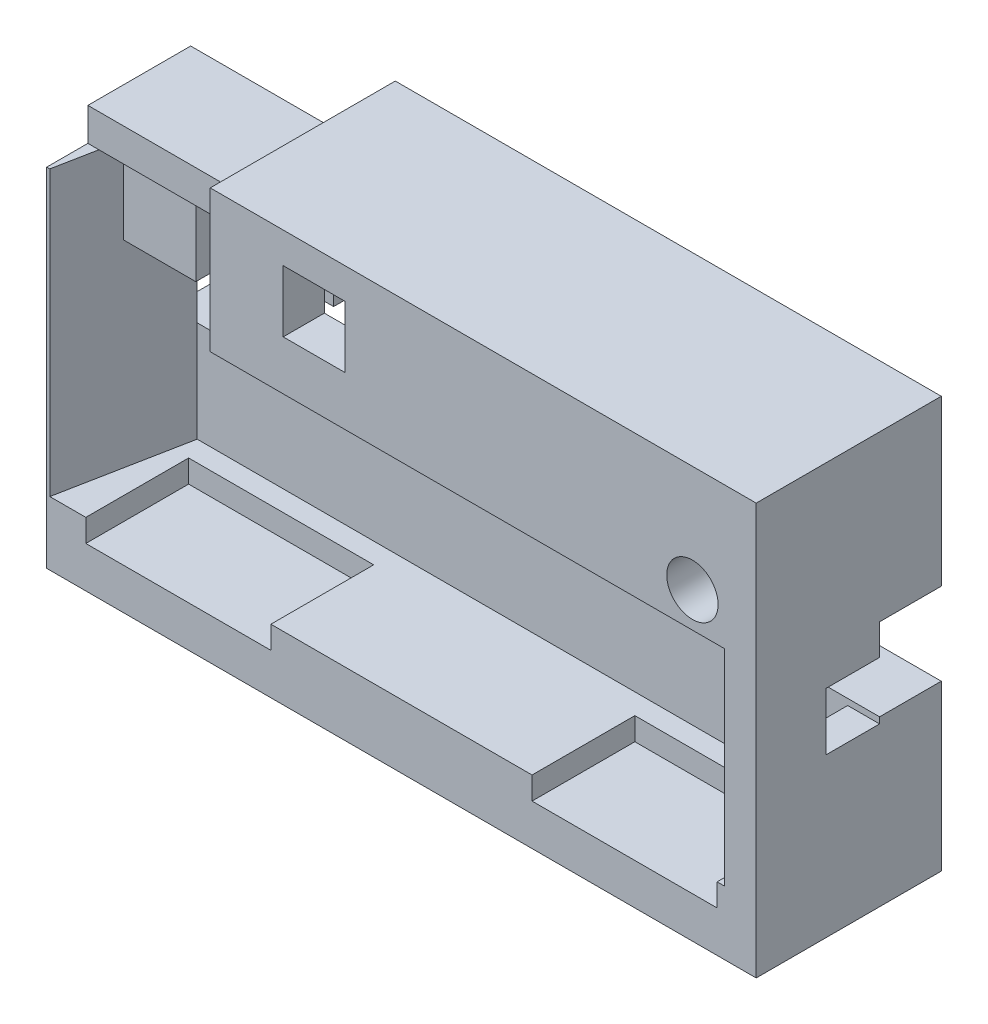
SolidWorks part; units mm, degrees
ref_plane "Ebene vorne" through (0, 0, 0) normal (0, 0, 1) x (1, 0, 0)
ref_plane "Ebene oben" through (0, 0, 0) normal (0, 1, 0) x (1, 0, 0)
ref_plane "Ebene rechts" through (0, 0, 0) normal (1, 0, 0) x (0, 0, -1)
sketch "Sketch1" plane through (0, 0, 0) normal (0, 0, 1) x (1, 0, 0)
  line L1 (-17.25, 10) -> (17.25, 10)
  line L2 (-17.25, 10) -> (-17.25, -10)
  line L3 (-17.25, -10) -> (17.25, -10)
  line L4 (17.25, 10) -> (17.25, -10)
  line L5 (-17.25, 10) -> (17.25, -10) construction
  line L6 (-17.25, -10) -> (17.25, 10) construction
  point P0 (0, 0)
  dimension "D1" = 34.5
  dimension "D2" = 20
extrude "Boss-Extrude1" add sketch "Sketch1" along normal blind 9
sketch "Sketch3" plane through (0, 0, 9) normal (0, 0, 1) x (1, 0, 0)
  line L1 (15.7, -6.9) -> (15.7, 3.1)
  line L3 (-15.7, 6.9) -> (-15.7, -6.9)
  line L6 (-15.7, 6.9) -> (-9.3, 6.9)
  line L7 (-15.7, -6.9) -> (15.7, -6.9)
  line L9 (-17.25, 10) -> (-17.25, -10) construction
  line L10 (-9.3, 6.9) -> (-9.3, 3.1)
  line L11 (-9.3, 3.1) -> (15.7, 3.1)
  point P2 (0, -6.9)
  dimension "D1" = 6.9
  dimension "D2" = 10
  dimension "D3" = 31.4
  dimension "D4" = 1.55
  dimension "D5" = 13.8
  dimension "D6" = 25
extrude "Cut-Extrude1" cut sketch "Sketch3" against normal blind 6
sketch "Sketch5" plane through (17.25, 0, 0) normal (1, 0, 0) x (0, 0, -1)
  line L0 (0, -2) -> (0, 2)
  line L1 (-3, 2) -> (0, 2)
  line L2 (-3, 2) -> (-3, -2)
  line L3 (-3, -2) -> (0, -2)
  point P0 (0, 0)
  dimension "D1" = 3
  dimension "D2" = 4
extrude "Cut-Extrude2" cut sketch "Sketch5" against normal blind 35
sketch "Sketch7" plane through (0, 0, 3) normal (0, 0, 1) x (1, 0, 0)
  line L0 (-9.3, 6.9) -> (-15.7, 6.9) construction
  line L4 (-13, 2.7) -> (-13, 6.9)
  line L5 (-13, 2.7) -> (-15.7, 2.7)
  line L6 (-15.7, 6.9) -> (-15.7, 2) construction
  line L7 (-15.7, 2.7) -> (-15.7, 6.9)
  line L8 (-15.7, 6.9) -> (-13, 6.9)
extrude "Boss-Extrude3" add sketch "Sketch7" along normal blind 3
sketch "Sketch8" plane through (0, 0, 9) normal (0, 0, 1) x (1, 0, 0)
  line L0 (-15.7, -6.9) -> (-15.35, -6.9) construction
  line L1 (-15.7, -6.9) -> (15.7, -6.9) construction
  line L2 (-15.35, -6.9) -> (-15.35, -8)
  line L3 (-15.35, -8) -> (-6.35, -8)
  line L4 (-6.35, -8) -> (-6.35, -6.9)
  line L5 (-6.35, -6.9) -> (-15.35, -6.9)
  line L6 (-17.25, 10) -> (-17.25, -10) construction
  line L7 (0, -4.95) -> (0, 4.95) construction
  line L8 (6.35, -6.9) -> (15.35, -6.9)
  line L9 (6.35, -8) -> (6.35, -6.9)
  line L10 (15.35, -8) -> (6.35, -8)
  line L11 (15.35, -6.9) -> (15.35, -8)
  line L12 (-9.3, 3.1) -> (-9.3, 6.9) construction
  circle A0 centre (14.1491, 4.8) radius 1.25
  point P21 (-9.3, 5)
  point P22 (10.85, -6.9)
  dimension "D4" = 2.5
  dimension "D1" = 1.9
  dimension "D2" = 1.1
  dimension "D3" = 9
  dimension "D5" = 23.45
  dimension "D6" = 11.7
sketch "Sketch14" plane through (0, 0, 3) normal (0, 0, 1) x (1, 0, 0)
  line L0 (-9.3, 6.9) -> (-15.7, 6.9) construction
  line L1 (-9.3, 3.1) -> (-9.3, 6.9) construction
  circle A0 centre (-11, 5.3) radius 0.75
  dimension "D3" = 1.5
  dimension "D1" = 1.6
  dimension "D2" = 1.7
extrude "Cut-Extrude9" cut sketch "Sketch14" against normal blind 2
extrude "Cut-Extrude3" cut sketch "Sketch8" against normal blind 5
chamfer "Chamfer1" distance 1.4 angle 79 1 edges at (-15.7, 0, 9) first distance on face at (-1.3286, -3.8143, 9)
sketch "Sketch6" plane through (0, 0, 0) normal (0, 0, -1) x (-1, 0, 0)
  line L0 (17.25, 10) -> (17.25, 2) construction
  line L5 (-17.25, 10) -> (17.25, 10) construction
  line L6 (-17.25, 10) -> (-17.25, 2) construction
  line L8 (17.25, 10) -> (17.25, 2) construction
  line L25 (-15.75, 8.5) -> (-15.75, 3.5)
  line L26 (-15.75, 3.5) -> (15.75, 3.5)
  line L27 (15.75, 8.5) -> (15.75, 3.5)
  line L28 (-15.75, 8.5) -> (15.75, 8.5)
  line L29 (4.95, 0) -> (-4.95, 0) construction
  line L30 (-15.75, -8.5) -> (15.75, -8.5)
  line L31 (15.75, -8.5) -> (15.75, -3.5)
  line L32 (-15.75, -3.5) -> (15.75, -3.5)
  line L33 (-15.75, -8.5) -> (-15.75, -3.5)
  line L34 (-17.25, 2) -> (17.25, 2) construction
  point P2 (0, 0)
  dimension "D2" = 1.5
  dimension "D3" = 5
extrude "Cut-Extrude6" cut sketch "Sketch6" against normal blind 2
sketch "Sketch11" plane through (17.25, 0, 0) normal (1, 0, 0) x (0, 0, -1)
  line L0 (-9, -10) -> (0, -10) construction
  line L3 (-5.6, 0.5) -> (-3, 0.5)
  line L4 (-5.6, 0.5) -> (-5.6, -2.3)
  line L5 (-5.6, -2.3) -> (-3, -2.3)
  line L6 (-3, 0.5) -> (-3, -2.3)
  line L7 (-9, -10) -> (-9, 10) construction
  point P0 (-5.6, 0.5)
  dimension "D1" = 3.4
  dimension "D2" = 7.7
  dimension "D3" = 2.8
  dimension "D4" = 2.6
extrude "Cut-Extrude7" cut sketch "Sketch11" against normal blind 2
sketch "Sketch12" plane through (0, 0, 2) normal (0, 0, -1) x (-1, 0, 0)
  line L6 (15.75, 8.5) -> (-15.75, 8.5) construction
  line L7 (2.75, 8.5) -> (5.75, 8.5)
  line L8 (2.75, 8.5) -> (2.75, 5.5)
  line L9 (2.75, 5.5) -> (5.75, 5.5)
  line L10 (5.75, 8.5) -> (5.75, 5.5)
  line L13 (15.75, 3.5) -> (15.75, 8.5) construction
  dimension "D1" = 3
  dimension "D2" = 3
  dimension "D3" = 3
  dimension "D4" = 10
extrude "Cut-Extrude8" cut sketch "Sketch12" against normal blind 7
sketch "Sketch16" plane through (0, 0, 9) normal (0, 0, 1) x (1, 0, 0)
  line L0 (-9.3, 3.1) -> (-9.3, 6.9) construction
  line L1 (-17.25, 10) -> (-9.3, 10)
  line L2 (-17.25, 10) -> (-17.25, 6.9)
  line L3 (-17.25, 6.9) -> (-9.3, 6.9)
  line L4 (-9.3, 10) -> (-9.3, 6.9)
  line L5 (-9.3, 3.1) -> (-9.3, 6.9) construction
extrude "Cut-Extrude10" cut sketch "Sketch16" against normal blind 2
sketch "Sketch17" plane through (0, 10, 0) normal (0, 1, 0) x (1, 0, 0)
  line L1 (-17.25, 0) -> (-9.3, 0)
  line L2 (-17.25, 0) -> (-17.25, -7)
  line L3 (-17.25, -7) -> (-9.3, -7)
  line L4 (-9.3, 0) -> (-9.3, -7)
extrude "Cut-Extrude11" cut sketch "Sketch17" against normal blind 1.5
sketch "Sketch18" plane through (0, 0, 0) normal (0, 0, 1) x (1, 0, 0)
  line L1 (-17.25, 8.5) -> (-15.75, 8.5)
  line L2 (-17.25, 8.5) -> (-17.25, 3.5)
  line L3 (-17.25, 3.5) -> (-15.75, 3.5)
  line L4 (-15.75, 8.5) -> (-15.75, 3.5)
extrude "Cut-Extrude12" cut sketch "Sketch18" along normal blind 2
sketch "Sketch20" plane through (0, 0, 0) normal (0, 0, -1) x (-1, 0, 0)
  line L0 (9.3, 8.5) -> (9.3, 2) construction
  line L1 (-17.25, 2) -> (17.25, 2) construction
  line L2 (-17.25, 2) -> (-17.25, 10) construction
  line L3 (9.3, 2) -> (-12.75, 2)
  line L4 (9.3, 2) -> (9.3, 5.75)
  line L5 (9.3, 5.75) -> (-12.75, 5.75)
  line L6 (-12.75, 2) -> (-12.75, 5.75)
  dimension "D1" = 3.75
  dimension "D2" = 4.5
extrude "Cut-Extrude13" cut sketch "Sketch20" against normal blind 7
sketch "Sketch21" plane through (0, 0, 2) normal (0, 0, -1) x (-1, 0, 0)
  line L0 (5.75, 5.75) -> (9.3, 5.75) construction
  line L1 (7.85, 5.75) -> (0.65, 5.75)
  line L2 (7.85, 5.75) -> (7.85, 8.5)
  line L3 (7.85, 8.5) -> (0.65, 8.5)
  line L4 (0.65, 5.75) -> (0.65, 8.5)
  line L5 (2.75, 8.5) -> (-15.75, 8.5) construction
  line L6 (2.75, 8.5) -> (2.75, 5.75) construction
  line L7 (5.75, 5.75) -> (5.75, 8.5) construction
  dimension "D1" = 2.1
  dimension "D2" = 2.1
extrude "Cut-Extrude14" cut sketch "Sketch21" against normal blind 5
